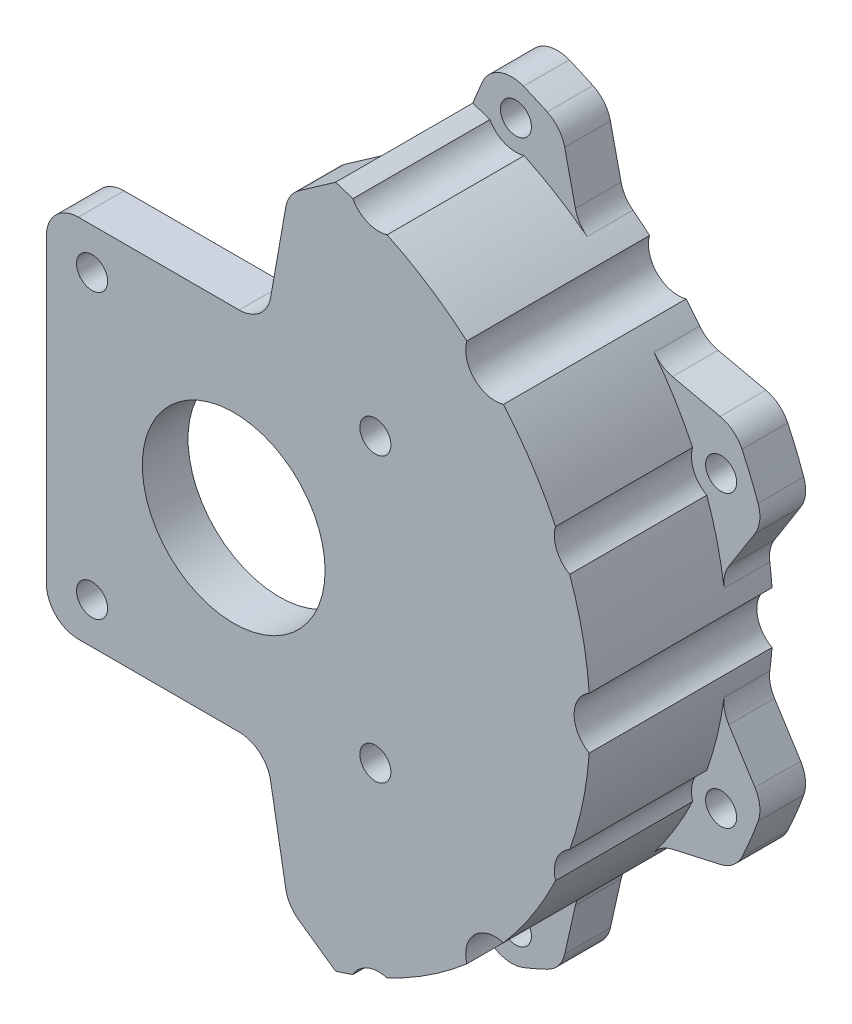
SolidWorks part; units mm, degrees
ref_plane "Alzado" through (0, 0, 0) normal (0, 0, 1) x (1, 0, 0)
ref_plane "Planta" through (0, 0, 0) normal (0, 1, 0) x (1, 0, 0)
ref_plane "Vista lateral" through (0, 0, 0) normal (1, 0, 0) x (0, 0, -1)
sketch "Croquis1" plane through (0, 0, 0) normal (0, 0, 1) x (1, 0, 0)
  line L0 (0, 0) -> (40.5, 0) construction
  line L1 (0, 0) -> (15.8814, 38.341) construction
  line L2 (13.4513, 42.9268) -> (10.7725, 36.4596)
  line L3 (0, 0) -> (38.341, 15.8814) construction
  line L4 (0, 0) -> (38.341, -15.8814) construction
  line L5 (0, 0) -> (15.8814, -38.341) construction
  line L7 (20.8423, 39.8653) -> (18.1635, 33.3982)
  line L8 (10.7725, 36.4596) -> (8.6471, 31.3285)
  line L9 (42.9268, 13.4513) -> (36.4596, 10.7725)
  line L10 (39.8653, 20.8423) -> (33.3982, 18.1635)
  line L11 (8.6471, -31.3285) -> (13.4513, -42.9268)
  line L12 (39.8653, -20.8423) -> (33.3982, -18.1635)
  line L13 (42.9268, -13.4513) -> (36.4596, -10.7725)
  line L16 (20.8423, -39.8653) -> (18.1635, -33.3982)
  line L18 (33.3982, 18.1635) -> (28.2671, 16.0382) [skipped]
  line L19 (36.4596, -10.7725) -> (31.3285, -8.6471) [skipped]
  line L20 (18.1635, -33.3982) -> (16.0382, -28.2671) [skipped]
  line L21 (13.4513, -42.9268) -> (8.6471, -31.3285) [skipped]
  circle A0 centre (0, 0) radius 40.5 construction
  circle A1 centre (15.8814, 38.341) radius 1.7
  circle A2 centre (0, 0) radius 41.5 construction
  circle A3 centre (0, 0) radius 41.5 construction
  circle A4 centre (38.341, 15.8814) radius 1.7
  circle A5 centre (0, 0) radius 41.5 construction
  circle A6 centre (38.341, -15.8814) radius 1.7
  circle A7 centre (0, 0) radius 41.5 construction
  circle A8 centre (15.8814, -38.341) radius 1.7
  arc A10 (13.4513, -42.9268) -> (20.8423, -39.8653) centre (0, 0) ccw
  arc A11 (8.6471, -31.3285) -> (8.6471, 31.3285) centre (0, 0) ccw
  arc A12 (33.3982, 18.1635) -> (18.1635, 33.3982) centre (0, 0) ccw
  arc A13 (36.4596, -10.7725) -> (36.4596, 10.7725) centre (0, 0) ccw
  arc A14 (18.1635, -33.3982) -> (33.3982, -18.1635) centre (0, 0) ccw
  arc A15 (39.8653, -20.8423) -> (42.9268, -13.4513) centre (0, 0) ccw
  arc A16 (42.9268, 13.4513) -> (39.8653, 20.8423) centre (0, 0) ccw
  arc A17 (20.8423, 39.8653) -> (13.4513, 42.9268) centre (0, 0) ccw
  point P9 (12.1119, 39.6932)
  point P22 (0, 0)
  point P45 (0, 0)
  dimension "D1" = 81
  dimension "D4" = 3.4
  dimension "D9" = 65
  dimension "D2" = 41.5
  dimension "D3" = 67.5
  dimension "D5" = 7
  dimension "D6" = 4
  dimension "D8" = 67.5
  dimension "D10" = 4
  dimension "D7" = 4
extrude "Saliente-Extruir1" add sketch "Croquis1" along normal blind 5
sketch "Croquis2" plane through (0, 0, 0) normal (0, 0, -1) x (-1, 0, 0)
  circle A0 centre (0, 0) radius 39.0124
extrude "Saliente-Extruir2" add sketch "Croquis2" against normal blind 20
sketch "Croquis3" plane through (0, 0, 20) normal (0, 0, 1) x (1, 0, 0)
  line L0 (0, 0) -> (-20.5, 0) construction
  line L1 (-15.5, -15.5) -> (15.5, -15.5) construction
  line L2 (-15.5, -15.5) -> (-15.5, 15.5) construction
  line L3 (-15.5, 15.5) -> (15.5, 15.5) construction
  line L4 (15.5, -15.5) -> (15.5, 15.5) construction
  line L5 (-15.5, -15.5) -> (15.5, 15.5) construction
  line L6 (-15.5, 15.5) -> (15.5, -15.5) construction
  line L7 (-20.5, 20) -> (-20.5, -20)
  line L8 (-20.5, 20) -> (3.5265, 20)
  line L9 (3.5265, 20) -> (6.7744, 38.4197)
  line L10 (3.5265, -20) -> (6.7744, -38.4197)
  line L11 (-20.5, -20) -> (3.5265, -20)
  circle A0 centre (-15.5, 15.5) radius 1.7
  circle A1 centre (15.5, 15.5) radius 1.7
  circle A2 centre (15.5, -15.5) radius 1.7
  circle A3 centre (-15.5, -15.5) radius 1.7
  circle A5 centre (0, 0) radius 39.0124 construction
  arc A6 (6.7744, 38.4197) -> (6.7744, -38.4197) centre (0, 0) ccw
  circle A7 centre (0, 0) radius 10
  point P0 (0, 0)
  point P16 (0, 0)
  point P18 (-20.5, 0)
  dimension "D3" = 3.4
  dimension "D6" = 20
  dimension "D2" = 31
  dimension "D4" = 40
  dimension "D5" = 20.5
  dimension "D7" = 100
  dimension "D1" = 4
extrude "Cortar-Extruir1" cut sketch "Croquis3" against normal blind 5
sketch "Croquis4" plane through (0, 0, 0) normal (0, 0, -1) x (-1, 0, 0)
  line L0 (-13.4513, 42.9268) -> (-11.1552, 37.3835)
  line L1 (-11.1552, 37.3835) -> (-9.8032, 34.1196)
  line L2 (0, 0) -> (35, 0) construction
  line L3 (-11.1552, -37.3835) -> (-9.8032, -34.1196)
  line L4 (-13.4513, -42.9268) -> (-11.1552, -37.3835)
  arc A0 (-9.8032, 34.1196) -> (-9.8032, -34.1196) centre (0, 0) ccw
  arc A1 (-13.4513, -42.9268) -> (-13.4513, 42.9268) centre (0, 0) ccw
  dimension "D1" = 71
  dimension "D2" = 44.985
extrude "Cortar-Extruir2" cut sketch "Croquis4" against normal blind 15
chamfer "Chaflán1" distance 4.75 angle 45 2 edges at (6.7744, 38.4197, 17.5) (6.7744, -38.4197, 17.5)
fillet "Redondeo2" radius 3.5 6 edges at (3.5265, 20, 17.5) (3.5265, -20, 17.5) (-20.5, -20, 17.5) (-20.5, 20, 17.5) (5.9496, -33.7419, 17.5) (5.9496, 33.7419, 17.5)
sketch "Croquis5" plane through (0, 0, 5) normal (0, 0, 1) x (1, 0, 0)
  circle A0 centre (15.8814, -38.341) radius 3.25
  dimension "D1" = 6.5
extrude "Cortar-Extruir3" cut sketch "Croquis5" along normal up to surface (15 mm away) up to face at (-13.8, -15.5, 20)
pattern_circular "MatrizC1" count 4 over 135 about axis through (0, 0, 20) along (0, 0, -1) of "Cortar-Extruir3" reverse direction yes
sketch "Croquis6" plane through (0, 0, 15) normal (0, 0, -1) x (-1, 0, 0)
  circle A0 centre (15.5, 15.5) radius 3.25
  circle A1 centre (15.5, -15.5) radius 3.25
  circle A2 centre (-15.5, -15.5) radius 3.25
  circle A3 centre (-15.5, 15.5) radius 3.25
  point P12 (0, 0)
  dimension "D1" = 6.5
  dimension "D2" = 4
extrude "Cortar-Extruir4" cut sketch "Croquis6" against normal blind 2.5
chamfer "Chaflán4" distance 2 angle 45 1 edges at (35.5, 0, 15)
sketch "Croquis8" plane through (0, 0, 0) normal (0, 0, -1) x (-1, 0, 0)
  line L0 (0, 0) -> (-50.5888, 0) construction
  line L5 (0, 0) -> (-38.341, -15.8814) construction
  circle A0 centre (-40.5, 0) radius 1.7 construction
  circle A1 centre (0, 0) radius 40.5 construction
  circle A2 centre (-28.6378, 28.6378) radius 1.7 construction
  circle A3 centre (0, 40.5) radius 1.7 construction
  circle A4 centre (28.6378, 28.6378) radius 1.7 construction
  circle A5 centre (40.5, 0) radius 1.7 construction
  circle A17 centre (-40.5, 0) radius 3.25
  circle A20 centre (-28.6378, -28.6378) radius 3.25
  circle A21 centre (-28.6378, 28.6378) radius 3.25
  point P17 (0, 0)
  dimension "D1" = 81
  dimension "D2" = 3.4
  dimension "D4" = 6.5
  dimension "D3" = 5
extrude "Cortar-Extruir5" cut sketch "Croquis8" against normal blind 32.5
chamfer "Chaflán5" distance 5.7 angle 45 6 edges at (34.3221, 18.5462, 2.5) (37.3835, 11.1552, 2.5) (37.3835, -11.1552, 2.5) (34.3221, -18.5462, 2.5) (18.5462, 34.3221, 2.5) (18.5462, -34.3221, 2.5) first distance on face at (33.1013, 20.3337, 8.3333) first distance on face at (37.7843, 9.0281, 8.3333) first distance on face at (37.7843, -9.0281, 8.3333) first distance on face at (33.1013, -20.3337, 8.3333) first distance on face at (20.3337, 33.1013, 8.3333) first distance on face at (20.3337, -33.1013, 8.3333)
fillet "Redondeo3" radius 3.5 14 edges at (31.7424, 22.68, 2.5) (39.8556, 20.8609, 2.5) (42.9331, 13.4313, 2.5) (38.4825, 6.4081, 2.5) (31.7424, -22.68, 2.5) (38.4825, -6.4081, 2.5) (42.9331, -13.4313, 2.5) (39.8556, -20.8609, 2.5) (13.4513, 42.9268, 2.5) (13.4513, -42.9268, 2.5) (20.8609, 39.8556, 2.5) (22.68, 31.7424, 2.5) (22.68, -31.7424, 2.5) (20.8609, -39.8556, 2.5)
